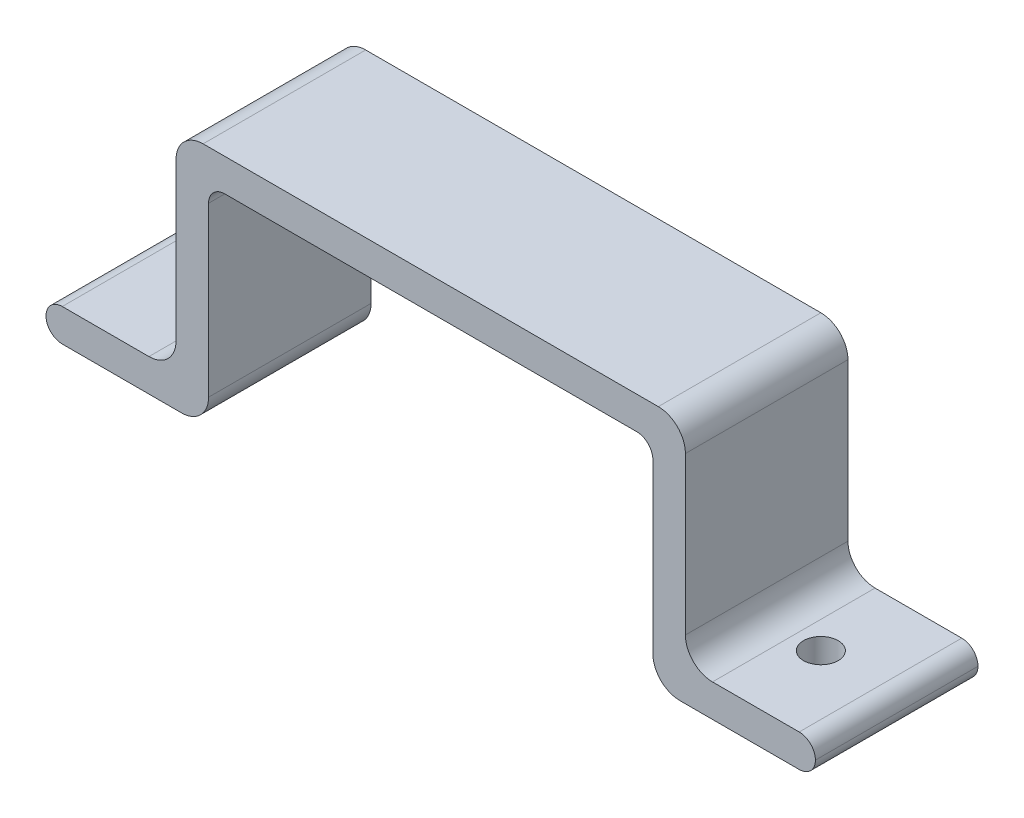
SolidWorks part; units mm, degrees
ref_plane "Front Plane" through (0, 0, 0) normal (0, 0, 1) x (1, 0, 0)
ref_plane "Top Plane" through (0, 0, 0) normal (0, 1, 0) x (1, 0, 0)
ref_plane "Right Plane" through (0, 0, 0) normal (1, 0, 0) x (0, 0, -1)
sketch "Sketch1" plane through (0, 0, 0) normal (0, 0, 1) x (1, 0, 0)
  line L0 (-23.5, 12.75) -> (23.5, 12.75)
  line L1 (23.5, 12.75) -> (23.5, -6.75)
  line L2 (23.5, -6.75) -> (35.5, -6.75)
  line L3 (35.5, -6.75) -> (35.5, -9.75)
  line L4 (35.5, -9.75) -> (20.5, -9.75)
  line L5 (20.5, -9.75) -> (20.5, 9.75)
  line L6 (20.5, 9.75) -> (-20.5, 9.75)
  line L7 (-20.5, 9.75) -> (-20.5, -9.75)
  line L8 (-20.5, -9.75) -> (-35.5, -9.75)
  line L9 (-35.5, -9.75) -> (-35.5, -6.75)
  line L10 (-35.5, -6.75) -> (-23.5, -6.75)
  line L11 (-23.5, -6.75) -> (-23.5, 12.75)
  line L12 (-23.5, 15.5222) -> (-20.5, 15.5222) construction
  line L13 (-10.112, 12.75) -> (-10.112, 9.75) construction
  line L14 (20.5, 12.1809) -> (23.5, 12.1809) construction
  point P3 (0, 12.75)
  point P19 (-35.5691, 18.2)
  point P20 (0, 0)
  point P22 (-20.5, 0)
  dimension "D1" = 41
  dimension "D2" = 3
  dimension "D3" = 19.5
  dimension "D4" = 15
extrude "Boss-Extrude1" add sketch "Sketch1" along normal mid plane 15
sketch "Sketch2" plane through (0, -6.75, 0) normal (0, 1, 0) x (1, 0, 0)
  line L0 (-35.5, -7.5) -> (-35.5, 7.5) construction
  line L1 (35.5, -7.5) -> (35.5, 7.5) construction
  line L2 (-35.5, 0) -> (-28.5, 0) construction
  line L3 (28.5, 0) -> (35.5, 0) construction
  circle A0 centre (-28.5, 0) radius 1.6
  circle A1 centre (28.5, 0) radius 1.6
  point P8 (-35.5, 0)
  point P12 (35.5, 0)
  dimension "D1" = 3.2
  dimension "D2" = 7
extrude "Cut-Extrude2" cut sketch "Sketch2" against normal through all
fillet "Fillet1" radius 2.5 6 edges at (-23.5, 12.75, 0) (23.5, 12.75, 0) (20.5, -9.75, 0) (23.5, -6.75, 0) (-20.5, -9.75, 0) (-23.5, -6.75, 0)
fillet "Fillet2" radius 1.5 6 edges at (35.5, -6.75, 0) (35.5, -9.75, 0) (20.5, 9.75, 0) (-20.5, 9.75, 0) (-35.5, -9.75, 0) (-35.5, -6.75, 0)
